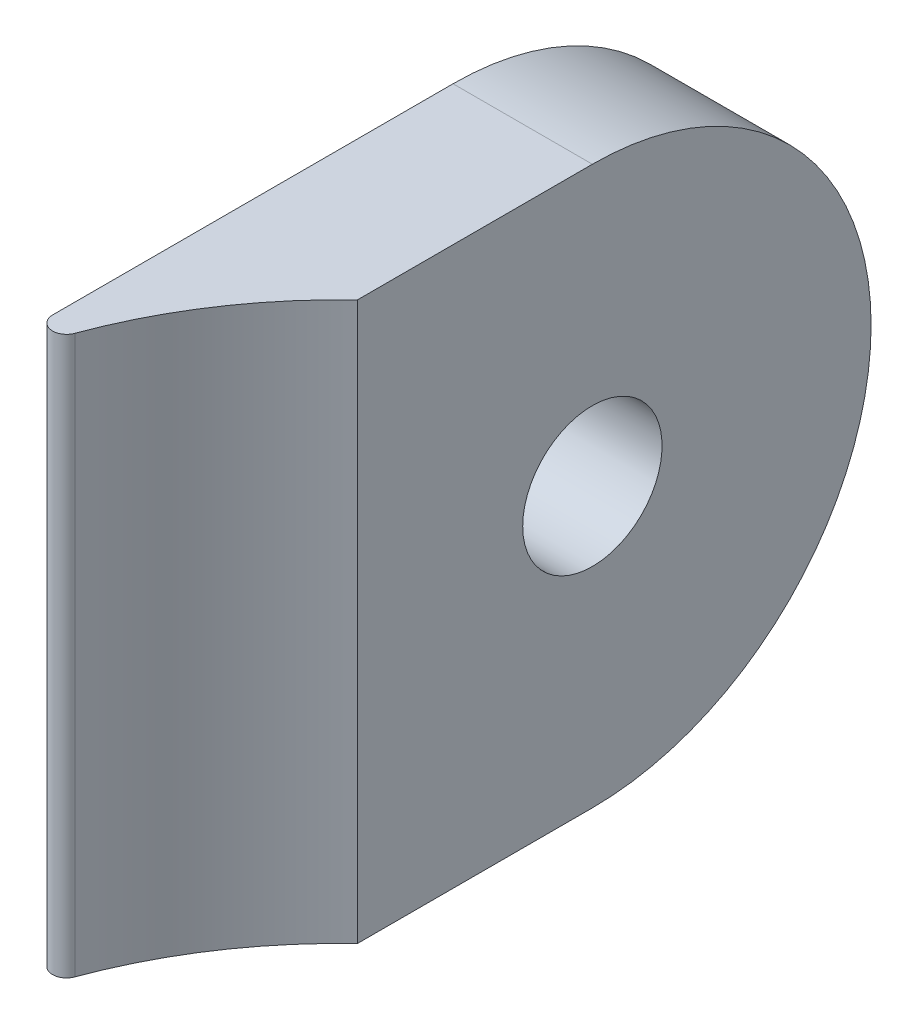
SolidWorks part; units mm, degrees
ref_plane "Front Plane" through (0, 0, 0) normal (0, 0, 1) x (1, 0, 0)
ref_plane "Top Plane" through (0, 0, 0) normal (0, 1, 0) x (1, 0, 0)
ref_plane "Right Plane" through (0, 0, 0) normal (1, 0, 0) x (0, 0, -1)
sketch "Sketch1" plane through (0, 0, 0) normal (0, 1, 0) x (1, 0, 0)
  line L0 (-15.875, 0) -> (-15.875, 30)
  line L1 (-15.875, 30) -> (-10.875, 30)
  line L2 (-10.875, 30) -> (-10.875, 11.565)
  arc A0 (-10.875, 11.565) -> (-15.875, 0) centre (0, 0) ccw
  dimension "D1" = 31.75
  dimension "D2" = 5
  dimension "D3" = 30
extrude "Boss-Extrude1" add sketch "Sketch1" along normal blind 20
fillet "Fillet1" radius 10 2 edges at (-13.375, 0, -30) (-13.375, 20, -30)
sketch "Sketch2" plane through (-15.875, 0, 0) normal (-1, 0, 0) x (0, 0, 1)
  line L0 (0, 89.4858) -> (0, -312.0666) construction
  circle A0 centre (-20, 10) radius 2.5
  dimension "D1" = 5
extrude "Cut-Extrude1" cut sketch "Sketch2" against normal through all contours A0
fillet "Fillet2" radius 0.5 1 edges at (-15.875, 10, 0)
